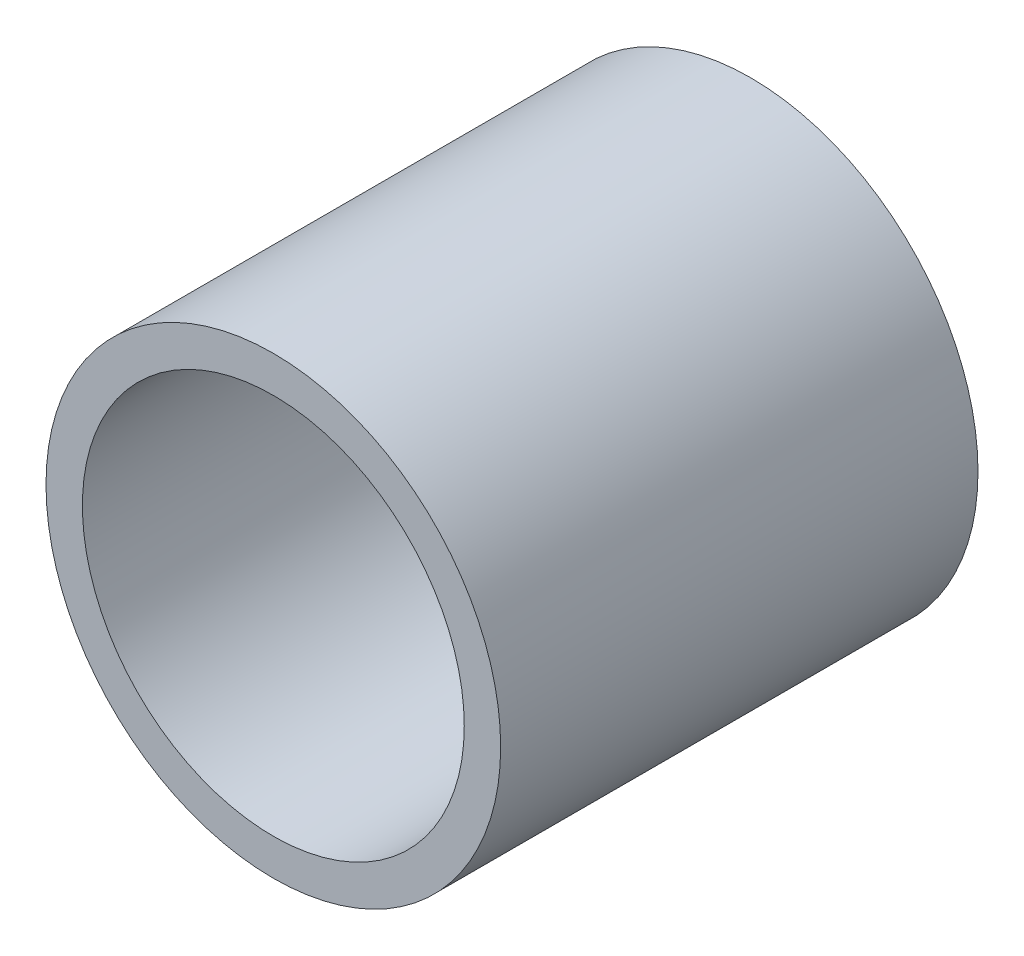
SolidWorks part; units mm, degrees
ref_plane "Front Plane" through (0, 0, 0) normal (0, 0, 1) x (1, 0, 0)
ref_plane "Top Plane" through (0, 0, 0) normal (0, 1, 0) x (1, 0, 0)
ref_plane "Right Plane" through (0, 0, 0) normal (1, 0, 0) x (0, 0, -1)
sketch "Sketch1" plane through (0, 0, 0) normal (0, 0, 1) x (1, 0, 0)
  circle A0 centre (0, 0) radius 24.1935
  circle A1 centre (0, 0) radius 20.32
  dimension "D1" = 40.64
  dimension "D2" = 48.387
extrude "Boss-Extrude1" add sketch "Sketch1" along normal blind 50.8
